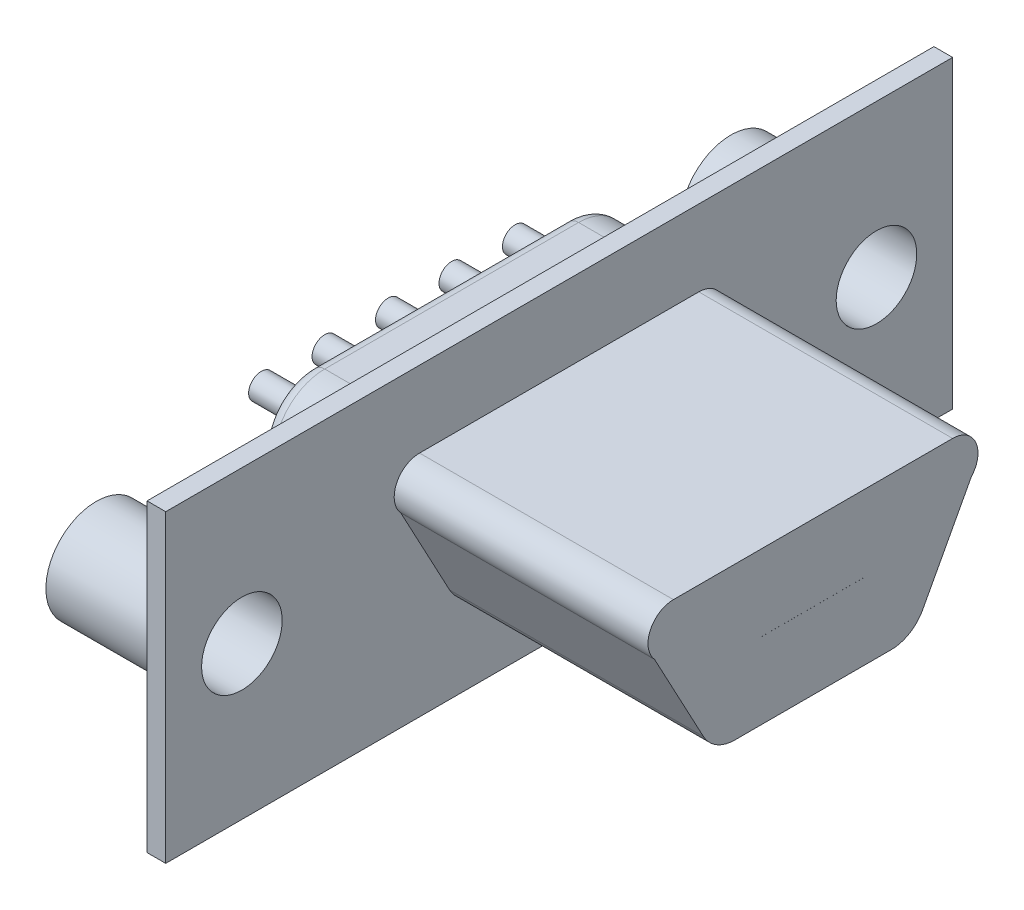
SolidWorks part; units mm, degrees
material "Plain Carbon Steel"
ref_plane "Front Plane" through (0, 0, 0) normal (0, 0, 1) x (1, 0, 0)
ref_plane "Top Plane" through (0, 0, 0) normal (0, 1, 0) x (1, 0, 0)
ref_plane "Right Plane" through (0, 0, 0) normal (1, 0, 0) x (0, 0, -1)
sketch "Sketch1" plane through (0, 0, 0) normal (1, 0, 0) x (0, 0, -1)
  line L1 (-15.5, -6) -> (15.5, -6)
  line L2 (-15.5, -6) -> (-15.5, 6)
  line L3 (-15.5, 6) -> (15.5, 6)
  line L4 (15.5, -6) -> (15.5, 6)
  line L5 (-15.5, -6) -> (15.5, 6) construction
  line L6 (-15.5, 6) -> (15.5, -6) construction
  point P0 (0, 0)
  dimension "D1" = 12
  dimension "D2" = 31
base flange "Base-Flange1" sketch "Sketch1" thickness 0.7366 reverse thickness direction no parameters "D1"=0.7366
sketch "Sketch6" plane through (0, 0, 0) normal (1, 0, 0) x (0, 0, -1)
  line L0 (0, 0) -> (0, 5.1271) construction
  line L1 (0, 3) -> (5.5, 3)
  line L2 (6.2399, 1.3273) -> (4.3174, -2.2612)
  line L3 (3.0833, -3) -> (0, -3)
  line L4 (0, 0) -> (0, -4.4714) construction
  line L5 (-10.9515, 0) -> (13.5174, 0) construction
  arc A0 (4.3174, -2.2612) -> (3.0833, -3) centre (3.0833, -1.6) cw
  arc A1 (5.5, 3) -> (6.2399, 1.3273) centre (5.5, 2) cw
  dimension "D2" = 1
  dimension "D3" = 1.4
  dimension "D1" = 5.5
  dimension "D4" = 3
  dimension "D5" = 4.071
  dimension "D6" = 4.3174
extrude "Extrude-Thin3" add sketch "Sketch6" along normal blind 10 thin thin type one direction wall 2.999
mirror "Mirror1" about plane through (0, 0, 0) normal (0, 0, 1) of "Extrude-Thin3"
sketch "Sketch8" plane through (-0.7366, 0, 0) normal (-1, 0, 0) x (0, 0, 1)
  line L1 (-7, -3.5) -> (7, -3.5)
  line L2 (-7, -3.5) -> (-7, 3.5)
  line L3 (-7, 3.5) -> (7, 3.5)
  line L4 (7, -3.5) -> (7, 3.5)
  line L5 (-7, -3.5) -> (7, 3.5) construction
  line L6 (-7, 3.5) -> (7, -3.5) construction
  point P0 (0, 0)
  dimension "D1" = 7
  dimension "D2" = 14
extrude "Boss-Extrude1" add sketch "Sketch8" along normal blind 4
fillet "Fillet2" radius 2 4 edges at (-2.7366, -3.5, 7) (-2.7366, 3.5, 7) (-2.7366, -3.5, -7) (-2.7366, 3.5, -7)
fillet "Fillet3" radius 0.5 8 edges at (-4.7366, -2.9142, -6.4142) (-4.7366, 0, -7) (-4.7366, 2.9142, -6.4142) (-4.7366, 3.5, 0) (-4.7366, 2.9142, 6.4142) (-4.7366, 0, 7) (-4.7366, -2.9142, 6.4142) (-4.7366, -3.5, 0)
sketch "Sketch9" plane through (-4.7366, 0, 0) normal (-1, 0, 0) x (0, 0, 1)
  line L0 (0, 0) -> (0, 9.3817) construction
  circle A0 centre (-5, 1.6731) radius 0.4986
  circle A1 centre (-2.5, 1.6731) radius 0.4986
  circle A2 centre (0, 1.6731) radius 0.4986
  circle A3 centre (2.5, 1.6731) radius 0.4986
  circle A4 centre (5, 1.6731) radius 0.4986
  dimension "D1" = 5
extrude "Boss-Extrude2" add sketch "Sketch9" along normal blind 2
sketch "Sketch10" plane through (-4.7366, 0, 0) normal (-1, 0, 0) x (0, 0, 1)
  line L1 (0, 0) -> (0, -9.2654) construction
  circle A0 centre (-3.75, -1.1156) radius 0.4986
  circle A1 centre (-1.25, -1.1156) radius 0.4986
  circle A2 centre (1.25, -1.1156) radius 0.4986
  circle A3 centre (3.75, -1.1156) radius 0.4986
  dimension "D1" = 0.9971
  dimension "D2" = 4
extrude "Boss-Extrude3" add sketch "Sketch10" along normal blind 2
sketch "Sketch11" plane through (-0.7366, 0, 0) normal (-1, 0, 0) x (0, 0, 1)
  line L0 (15.5, -6) -> (-15.5, -6) construction
  circle A0 centre (-12.5, 0) radius 1.9844
  dimension "D1" = 3.9688
  dimension "D3" = 12.5
  dimension "D2" = 6
extrude "Boss-Extrude4" add sketch "Sketch11" along normal blind 5
mirror "Mirror2" about plane through (0, 0, 0) normal (0, 0, 1) of "Boss-Extrude4"
hole_wizard "1/8 (0.125) Diameter Hole1" positions "Sketch13" profile "Sketch14" hole size "1/8" standard "ANSI Inch" end condition through all
sketch "Sketch13" plane through (-5.7366, 0, 0) normal (-1, 0, 0) x (0, 0, 1)
  point P0 (-12.5, 0)
sketch "Sketch14" plane through (-5.7366, 0, -12.5) normal (0, 1, 0) x (0, 0, 1)
  line L0 (0, 0) -> (0, 15.7366)
  line L1 (0, 15.7366) -> (1.5875, 15.7366)
  line L2 (1.5875, 15.7366) -> (1.5875, 0)
  line L5 (1.5875, 0) -> (0, 0)
  line L11 (0, -6.35) -> (0, 107.95) construction
  dimension "Thru Hole Dia." = 3.175
  dimension "Thru Hole Depth" = 15.7366
mirror "Mirror3" about plane through (0, 0, 0) normal (0, 0, 1) of "1/8 (0.125) Diameter Hole1"
sketch "Bend-Lines1" plane through (0, 0, 0) normal (0, 1, 0) x (1, 0, 0)
sketch "Bounding-Box1" plane through (0, 0, 0) normal (0, 1, 0) x (1, 0, 0)
sheet metal parameters "Sheet-Metal3" thickness 0.7366 parameters "D1"=0.7366
flat pattern "Flat-Pattern3" [suppressed]
sketch "Bend-Lines2" plane through (0, 0, 0) normal (0, 1, 0) x (1, 0, 0)
sketch "Bounding-Box2" [suppressed] plane through (0, 0, 0) normal (0, 1, 0) x (1, 0, 0)
sheet metal parameters "Sheet-Metal4" thickness 0.7366 parameters "D1"=0.7366
flat pattern "Flat-Pattern3"
sketch "Bend-Lines2" plane through (0, 0, 0) normal (0, 1, 0) x (1, 0, 0)
sketch "Bounding-Box2" [suppressed] plane through (0, 0, 0) normal (0, 1, 0) x (1, 0, 0)
sheet metal parameters "Sheet-Metal5" thickness 0.7366 parameters "D1"=0.7366
flat pattern "Flat-Pattern3"
sketch "Bend-Lines2" plane through (0, 0, 0) normal (0, 1, 0) x (1, 0, 0)
sketch "Bounding-Box2" [suppressed] plane through (0, 0, 0) normal (0, 1, 0) x (1, 0, 0)
sheet metal parameters "Sheet-Metal6" thickness 0.7366 parameters "D1"=0.7366
flat pattern "Flat-Pattern3"
sketch "Bend-Lines2" plane through (0, 0, 0) normal (0, 1, 0) x (1, 0, 0)
sketch "Bounding-Box2" [suppressed] plane through (0, 0, 0) normal (0, 1, 0) x (1, 0, 0)
sheet metal parameters "Sheet-Metal7" thickness 0.7366 parameters "D1"=0.7366
flat pattern "Flat-Pattern3"
sketch "Bend-Lines2" plane through (0, 0, 0) normal (0, 1, 0) x (1, 0, 0)
sketch "Bounding-Box2" [suppressed] plane through (0, 0, 0) normal (0, 1, 0) x (1, 0, 0)
sheet metal parameters "Sheet-Metal8" thickness 0.7366 parameters "D1"=0.7366
flat pattern "Flat-Pattern3"
sketch "Bend-Lines2" plane through (0, 0, 0) normal (0, 1, 0) x (1, 0, 0)
sketch "Bounding-Box2" [suppressed] plane through (0, 0, 0) normal (0, 1, 0) x (1, 0, 0)
sheet metal parameters "Sheet-Metal9" thickness 0.7366 parameters "D1"=0.7366
flat pattern "Flat-Pattern3"
sketch "Bend-Lines2" plane through (0, 0, 0) normal (0, 1, 0) x (1, 0, 0)
sketch "Bounding-Box2" [suppressed] plane through (0, 0, 0) normal (0, 1, 0) x (1, 0, 0)
sheet metal parameters "Sheet-Metal10" thickness 0.7366 parameters "D1"=0.7366
flat pattern "Flat-Pattern3"
sketch "Bend-Lines2" plane through (0, 0, 0) normal (0, 1, 0) x (1, 0, 0)
sketch "Bounding-Box2" [suppressed] plane through (0, 0, 0) normal (0, 1, 0) x (1, 0, 0)
sheet metal parameters "Sheet-Metal11" thickness 0.7366 parameters "D1"=0.7366
flat pattern "Flat-Pattern3"
sketch "Bend-Lines2" plane through (0, 0, 0) normal (0, 1, 0) x (1, 0, 0)
sketch "Bounding-Box2" [suppressed] plane through (0, 0, 0) normal (0, 1, 0) x (1, 0, 0)
sheet metal parameters "Sheet-Metal12" thickness 0.7366 parameters "D1"=0.7366
flat pattern "Flat-Pattern3"
sketch "Bend-Lines2" plane through (0, 0, 0) normal (0, 1, 0) x (1, 0, 0)
sketch "Bounding-Box2" [suppressed] plane through (0, 0, 0) normal (0, 1, 0) x (1, 0, 0)
